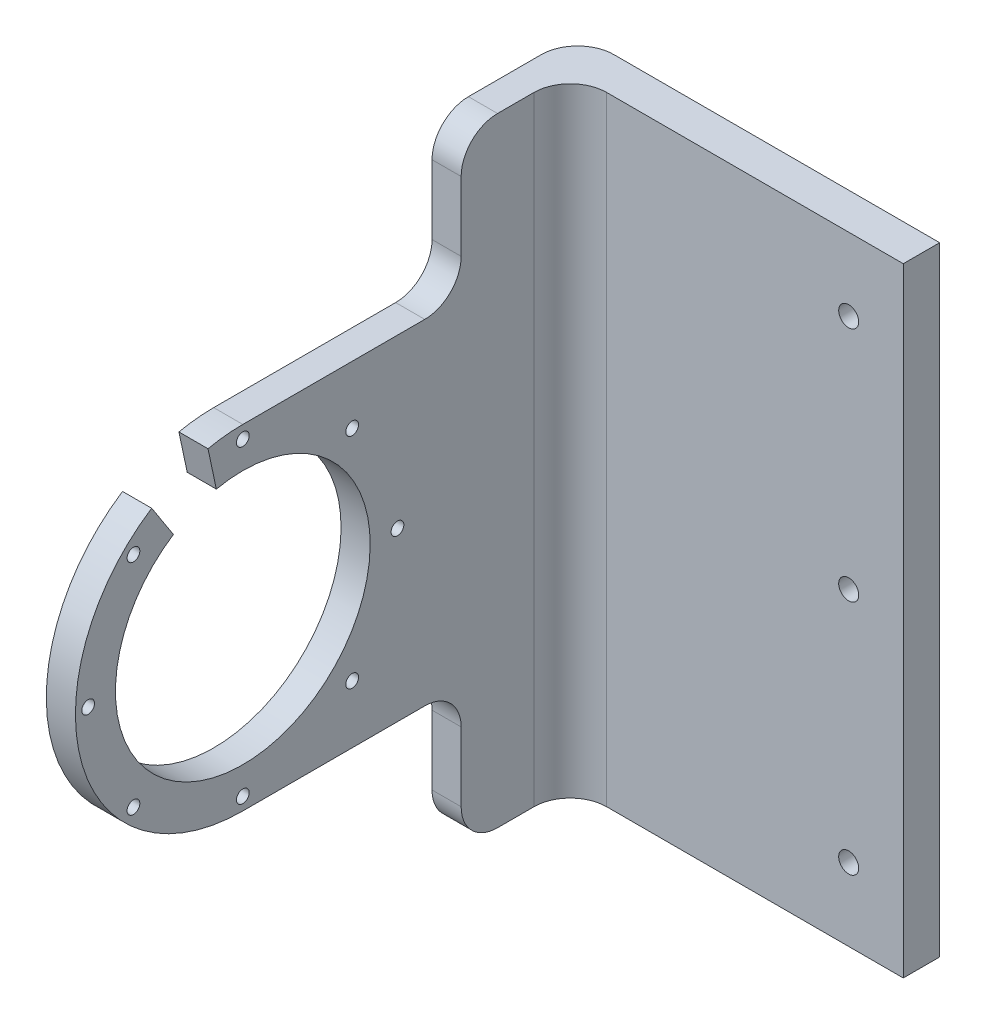
SolidWorks part; units mm, degrees
material "6061 合金"
ref_plane "前视基准面" through (0, 0, 0) normal (0, 0, 1) x (1, 0, 0)
ref_plane "上视基准面" through (0, 0, 0) normal (0, 1, 0) x (1, 0, 0)
ref_plane "右视基准面" through (0, 0, 0) normal (1, 0, 0) x (0, 0, -1)
other "Configuration Table"
sketch "草图1" plane through (0, 0, 0) normal (0, 1, 0) x (1, 0, 0)
  line L0 (0, 0) -> (111.3, 0) construction
  line L1 (111.3, 0) -> (111.3, -10) construction
  line L2 (111.3, -10) -> (8, -10) construction
  line L3 (8, -10) -> (8, -300)
  line L4 (8, -300) -> (0, -300)
  line L5 (0, -300) -> (0, 0)
  line L6 (8, -10) -> (8, 0)
  line L7 (0, 0) -> (8, 0)
  dimension "D1" = 103.3
  dimension "D2" = 290
  dimension "D3" = 10
  dimension "D4" = 8
extrude "凸台-拉伸1" add sketch "草图1" along normal blind 170
sketch "草图2" plane through (8, 0, 0) normal (1, 0, 0) x (0, 0, -1)
  line L0 (-318.0541, 85) -> (-40.874, 85) construction
  line L1 (-300, 170) -> (0, 170) construction
  line L2 (-300, 0) -> (0, 0) construction
  line L7 (0, 170) -> (0, 0) construction
  line L9 (-100, 131) -> (-40, 131)
  line L10 (-40, 131) -> (-40, 170)
  line L11 (-300, 170) -> (0, 170) construction
  line L12 (-100, 39) -> (-40, 39)
  line L13 (-40, 39) -> (-40, 0)
  line L14 (-40, 170) -> (-300, 170)
  line L15 (-300, 170) -> (-300, 0)
  line L16 (-300, 0) -> (-40, 0)
  arc A0 (-100, 131) -> (-100, 39) centre (-100, 85) ccw
  circle A1 centre (-100, 85) radius 35
  dimension "D2" = 70
  dimension "D3" = 46
  dimension "D1" = 100
  dimension "D4" = 40
extrude "切除-拉伸1" cut sketch "草图2" against normal blind 180
sketch "草图5" plane through (8, 0, 0) normal (1, 0, 0) x (0, 0, -1)
  line L0 (-40, 170) -> (0, 170) construction
  line L1 (0, 0) -> (-10, 0)
  line L2 (0, 0) -> (0, 170)
  line L3 (0, 170) -> (-10, 170)
  line L4 (-10, 0) -> (-10, 170)
  dimension "D1" = 10
extrude "凸台-拉伸3" add sketch "草图5" along normal blind 101.5
other "移动面1" [suppressed] flip direction yes offset 15 parameters "D1"=15
sketch "草图6" plane through (0, 0, 0) normal (0, 0, -1) x (-1, 0, 0)
  line L0 (-109.5, 0) -> (-109.5, 170) construction
  line L1 (-109.5, 0) -> (-109.5, 170) construction
  line L2 (-109.5, 170) -> (0, 170) construction
  line L3 (-109.5, 0) -> (0, 0) construction
  circle A0 centre (-84.5, 150) radius 2.75
  circle A1 centre (-84.5, 20) radius 2.75
  circle A2 centre (-84.5, 85) radius 2.75
  dimension "D1" = 5.5
  dimension "D2" = 25
  dimension "D3" = 20
  dimension "D4" = 20
  dimension "D5" = 65
extrude "切除-拉伸3" cut sketch "草图6" against normal blind 52
sketch "草图8" plane through (0, 0, 0) normal (-1, 0, 0) x (0, 0, 1)
  line L3 (0, 0) -> (40, 0)
  line L4 (40, 170) -> (0, 170)
  line L5 (0, 170) -> (0, 0)
  line L6 (0, 0) -> (40, 0) construction
  line L7 (40, 170) -> (0, 170) construction
  line L8 (0, 170) -> (0, 0) construction
  line L13 (40, 0) -> (40, 39)
  line L14 (40, 0) -> (40, 39)
  line L15 (40, 39) -> (100, 39)
  line L16 (40, 39) -> (100, 39)
  line L17 (100, 131) -> (40, 131)
  line L18 (100, 131) -> (40, 131)
  line L19 (40, 131) -> (40, 170)
  line L20 (40, 131) -> (40, 170)
  arc A0 (58.008, 157.6182) -> (53.4765, 159.7313) centre (55.7423, 158.6748) ccw construction
  arc A1 (100, 39) -> (100, 131) centre (100, 85) ccw
  arc A2 (100, 39) -> (100, 131) centre (100, 85) ccw construction
  arc A3 (58.008, 157.6182) -> (53.4765, 159.7313) centre (55.7423, 158.6748) ccw construction
  arc A4 (30.2194, 143.4465) -> (34.751, 141.3335) centre (32.4852, 142.39) ccw construction
  arc A5 (6.8011, 93.2258) -> (11.3327, 91.1128) centre (9.0669, 92.1693) ccw construction
  arc A6 (9.2756, 64.9423) -> (13.8072, 62.8292) centre (11.5414, 63.8857) ccw construction
  arc A7 (14.0595, 51.7988) -> (18.591, 49.6857) centre (16.3252, 50.7423) ccw construction
  arc A8 (30.3442, 28.5418) -> (34.8758, 26.4287) centre (32.61, 27.4852) ccw construction
  arc A9 (80.5649, 5.1235) -> (85.0965, 3.0104) centre (82.8307, 4.0669) ccw construction
  arc A10 (113.38, 5.4849) -> (108.8485, 7.598) centre (111.1143, 6.5414) ccw construction
  arc A11 (126.5235, 10.2687) -> (121.992, 12.3818) centre (124.2577, 11.3252) ccw construction
  arc A12 (149.7806, 26.5535) -> (145.249, 28.6665) centre (147.5148, 27.61) ccw construction
  arc A13 (173.1989, 76.7742) -> (168.6673, 78.8872) centre (170.9331, 77.8307) ccw construction
  arc A14 (170.7244, 105.0577) -> (166.1928, 107.1708) centre (168.4586, 106.1143) ccw construction
  arc A15 (165.9405, 118.2012) -> (161.409, 120.3143) centre (163.6748, 119.2577) ccw construction
  arc A16 (149.6558, 141.4582) -> (145.1242, 143.5713) centre (147.39, 142.5148) ccw construction
  arc A17 (99.4351, 164.8765) -> (94.9035, 166.9896) centre (97.1693, 165.9331) ccw construction
  arc A18 (58.008, 157.6182) -> (53.4765, 159.7313) centre (55.7423, 158.6748) ccw construction
  arc A19 (30.2194, 143.4465) -> (34.751, 141.3335) centre (32.4852, 142.39) ccw construction
  arc A20 (6.8011, 93.2258) -> (11.3327, 91.1128) centre (9.0669, 92.1693) ccw construction
  arc A21 (9.2756, 64.9423) -> (13.8072, 62.8292) centre (11.5414, 63.8857) ccw construction
  arc A22 (14.0595, 51.7988) -> (18.591, 49.6857) centre (16.3252, 50.7423) ccw construction
  arc A23 (30.3442, 28.5418) -> (34.8758, 26.4287) centre (32.61, 27.4852) ccw construction
  arc A24 (80.5649, 5.1235) -> (85.0965, 3.0104) centre (82.8307, 4.0669) ccw construction
  arc A25 (113.38, 5.4849) -> (108.8485, 7.598) centre (111.1143, 6.5414) ccw construction
  arc A26 (126.5235, 10.2687) -> (121.992, 12.3818) centre (124.2577, 11.3252) ccw construction
  arc A27 (149.7806, 26.5535) -> (145.249, 28.6665) centre (147.5148, 27.61) ccw construction
  arc A28 (173.1989, 76.7742) -> (168.6673, 78.8872) centre (170.9331, 77.8307) ccw construction
  arc A29 (170.7244, 105.0577) -> (166.1928, 107.1708) centre (168.4586, 106.1143) ccw construction
  arc A30 (165.9405, 118.2012) -> (161.409, 120.3143) centre (163.6748, 119.2577) ccw construction
  arc A31 (149.6558, 141.4582) -> (145.1242, 143.5713) centre (147.39, 142.5148) ccw construction
  arc A32 (99.4351, 164.8765) -> (94.9035, 166.9896) centre (97.1693, 165.9331) ccw construction
  circle A33 centre (55.7423, 158.6748) radius 2.5
  circle A34 centre (97.1693, 165.9331) radius 2.5
  circle A35 centre (147.39, 142.5148) radius 2.5
  circle A36 centre (163.6748, 119.2577) radius 2.5
  circle A37 centre (168.4586, 106.1143) radius 2.5
  circle A38 centre (170.9331, 77.8307) radius 2.5
  circle A39 centre (147.5148, 27.61) radius 2.5
  circle A40 centre (124.2577, 11.3252) radius 2.5
  circle A41 centre (111.1143, 6.5414) radius 2.5
  circle A42 centre (82.8307, 4.0669) radius 2.5
  circle A43 centre (32.61, 27.4852) radius 2.5
  circle A44 centre (16.3252, 50.7423) radius 2.5
  circle A45 centre (11.5414, 63.8857) radius 2.5
  circle A46 centre (9.0669, 92.1693) radius 2.5
  circle A47 centre (32.4852, 142.39) radius 2.5
  dimension "D1" = 0
extrude "切除-拉伸4" [suppressed] cut sketch "草图8" against normal blind 52 contours A47 | A34 | A35 | A36 | A37 | A38 | A39 | A40 | A41 | A42 | A43 | A33
fillet "圆角2" radius 10 4 edges at (4, 170, 40) (4, 131, 40) (4, 0, 40) (4, 39, 40)
sketch "草图11" plane through (0, 0, 0) normal (-1, 0, 0) x (0, 0, 1)
  line L0 (100, 140.5507) -> (100, 30.313) construction
  circle A0 centre (100, 85) radius 35 construction
  circle A1 centre (100, 85) radius 35 construction
  circle A3 centre (100, 42.5) radius 1.75
  circle A4 centre (69.948, 54.948) radius 1.75
  circle A5 centre (57.5, 85) radius 1.75
  circle A6 centre (69.948, 115.052) radius 1.75
  circle A7 centre (100, 127.5) radius 1.75
  circle A8 centre (130.052, 115.052) radius 1.75
  circle A9 centre (142.5, 85) radius 1.75
  circle A10 centre (130.052, 54.948) radius 1.75
  point P23 (100, 85)
  dimension "D1" = 3.5
  dimension "D2" = 42.5
  dimension "D3" = 8
extrude "切除-拉伸5" cut sketch "草图11" against normal blind 10 contours A10 | A3 | A6 | A7 | A8 | A9 | A4 | A5 region at (0, 42.5, 100) region at (0, 115.052, 69.948) region at (0, 127.5, 100) region at (0, 115.052, 130.052) region at (0, 54.948, 130.052)
sketch "草图12" plane through (0, 0, 0) normal (-1, 0, 0) x (0, 0, 1)
  line L0 (100, 85) -> (110.3956, 133.9074)
  line L1 (100, 85) -> (127.232, 126.9335)
  line L2 (100, 85) -> (130.052, 115.052) construction
  line L3 (100, 85) -> (100, 127.5) construction
  arc A0 (110.3956, 133.9074) -> (127.232, 126.9335) centre (100, 85) cw
  dimension "D1" = 12
  dimension "D2" = 12
  dimension "D3" = 50
extrude "切除-拉伸6" cut sketch "草图12" against normal blind 13 contours A0 L1 L0
other "移动面2" flip direction yes face at (109.5, 85, 5) offset 10 parameters "D1"=10
fillet "圆角3" radius 10 2 edges at (0, 85, 0) (8, 85, 10)
